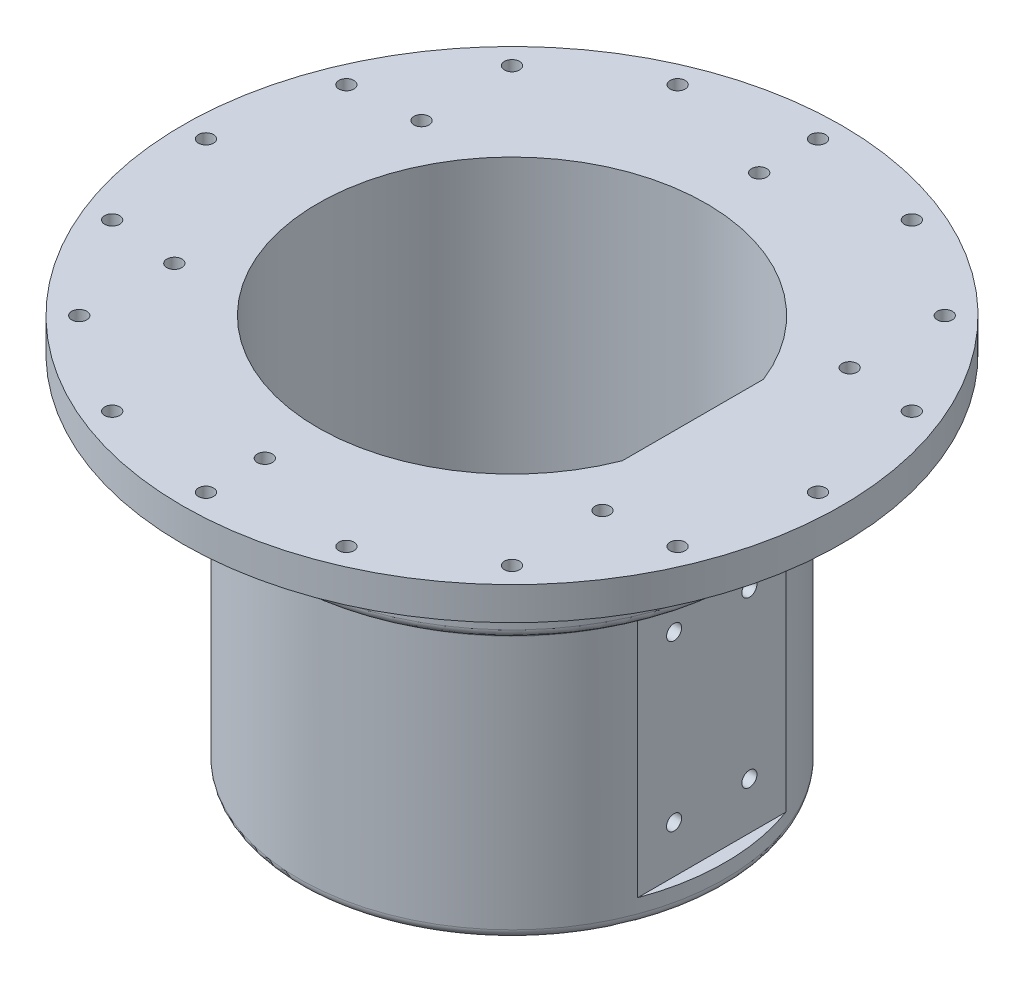
SolidWorks part; units mm, degrees
ref_plane "Front Plane" through (0, 0, 0) normal (0, 0, 1) x (1, 0, 0)
ref_plane "Top Plane" through (0, 0, 0) normal (0, 1, 0) x (1, 0, 0)
ref_plane "Right Plane" through (0, 0, 0) normal (1, 0, 0) x (0, 0, -1)
sketch "Sketch1" plane through (0, 0, 0) normal (0, 1, 0) x (1, 0, 0)
  circle A0 centre (0, 0) radius 49.25
  circle A1 centre (0, 0) radius 55 construction
  circle A2 centre (0, 0) radius 60
  circle A3 centre (0, 0) radius 52.5 construction
  circle A4 centre (0, 52.5) radius 1.6
  circle A5 centre (45.4663, 26.25) radius 1.6
  circle A6 centre (45.4663, -26.25) radius 1.6
  circle A7 centre (0, -52.5) radius 1.6
  circle A8 centre (-45.4663, -26.25) radius 1.6
  circle A9 centre (-45.4663, 26.25) radius 1.6
  point P9 (0, 0)
  point P10 (0, 0)
  point P20 (0, 0)
  dimension "D1" = 110
  dimension "D2" = 98.5
  dimension "D3" = 120
  dimension "D4" = 105
  dimension "D5" = 3.2
  dimension "D6" = 6
extrude "Boss-Extrude1" add sketch "Sketch1" along normal blind 7
sketch "Sketch2" plane through (0, 7, 0) normal (0, 1, 0) x (1, 0, 0)
  line L0 (0, 0) -> (29.4576, 0) construction
  line L1 (29.4576, 12.5) -> (60, 12.5) construction
  line L2 (29.4576, 12.5) -> (29.4576, -12.5) construction
  line L3 (29.4576, -12.5) -> (60, -12.5) construction
  line L4 (60, 12.5) -> (60, -12.5) construction
  circle A0 centre (0, 0) radius 49.25
  circle A2 centre (0, 0) radius 49.25 construction
  circle A3 centre (0, 0) radius 32 construction
  circle A5 centre (0, 0) radius 60 construction
  circle A6 centre (0, 0) radius 45.25
  point P8 (33.7602, 12.5)
  point P19 (33.7602, -12.5)
  circle M6 centre (0, 0) radius 49.25
  dimension "D1" = 4
  dimension "D2" = 64
  dimension "D3" = 25
extrude "Boss-Extrude2" add sketch "Sketch2" against normal blind 25 contours A6 M6 region at (-47.857, 7, 0)
sketch "Sketch6" plane through (0, 7, 0) normal (0, 1, 0) x (1, 0, 0)
  line L1 (38.4261, 15) -> (60, 15)
  line L2 (38.4261, 15) -> (38.4261, -15)
  line L3 (38.4261, -15) -> (60, -15)
  line L4 (60, 15) -> (60, -15)
  circle A0 centre (0, 0) radius 45.25
  circle A1 centre (0, 0) radius 41.25
  circle A2 centre (0, 0) radius 45.25 construction
  circle A3 centre (0, 0) radius 60 construction
  point P10 (0, 0)
  point P11 (38.4261, 0)
  point P14 (38.3377, 11.4114)
  circle M14 centre (0, 0) radius 45.25
  dimension "D1" = 4
  dimension "D2" = 30
extrude "Boss-Extrude5" add sketch "Sketch6" against normal blind 78 contours A1 L1 L3 M14 | L2 A1 | A1 L3 L1 M14 region at (-42.5119, 7, 0) region at (39.559, 7, 0) region at (42.3493, 7, 0)
sketch "Sketch7" plane through (0, -71, 0) normal (0, -1, 0) x (1, 0, 0)
  line L0 (38.4261, -15) -> (38.4261, 15) construction
  line L1 (42.4261, 15.735) -> (60, 15.735)
  line L2 (42.4261, 15.735) -> (42.4261, -15.735)
  line L3 (42.4261, -15.735) -> (60, -15.735)
  line L4 (60, 15.735) -> (60, -15.735)
  circle A0 centre (0, 0) radius 45.25 construction
  circle A1 centre (0, 0) radius 45.25 construction
  circle A2 centre (0, 0) radius 60 construction
  point P6 (41.1316, -15.6267)
  point P9 (42.4261, 0)
  dimension "D1" = 4
extrude "Cut-Extrude3" cut sketch "Sketch7" against normal up to surface (53 mm away) up to face at (0, -18, 45.25)
sketch "Sketch8" plane through (0, -71, 0) normal (0, -1, 0) x (1, 0, 0)
  circle A0 centre (0, 0) radius 45.25
  arc A1 (42.4261, 15.735) -> (42.4261, -15.735) centre (0, 0) ccw construction
  circle A2 centre (0, 0) radius 32
  circle A3 centre (0, 0) radius 37.75 construction
  circle A4 centre (26.6933, 26.6933) radius 1.6
  circle A5 centre (37.75, 0) radius 1.6
  circle A6 centre (26.6933, -26.6933) radius 1.6
  circle A7 centre (0, -37.75) radius 1.6
  circle A8 centre (-26.6933, -26.6933) radius 1.6
  circle A9 centre (-37.75, 0) radius 1.6
  circle A10 centre (-26.6933, 26.6933) radius 1.6
  circle A11 centre (0, 37.75) radius 1.6
  point P10 (0, 0)
  point P11 (36.5, 0)
  point P19 (0, 0)
  dimension "D1" = 7.5
  dimension "D2" = 64
  dimension "D3" = 3.2
  dimension "D4" = 8
extrude "Boss-Extrude6" add sketch "Sketch8" along normal blind 5
sketch "Sketch9" plane through (42.4261, 0, 0) normal (1, 0, 0) x (0, 0, -1)
  line L0 (15.735, -71) -> (-15.735, -71) construction
  line L1 (-8, -26) -> (8, -26) construction
  line L2 (-8, -26) -> (-8, -61) construction
  line L3 (-8, -61) -> (8, -61) construction
  line L4 (8, -26) -> (8, -61) construction
  circle A0 centre (-8, -26) radius 1.6
  circle A1 centre (8, -26) radius 1.6
  circle A2 centre (8, -61) radius 1.6
  circle A3 centre (-8, -61) radius 1.6
  point P4 (0, -26)
  dimension "D4" = 3.2
  dimension "D1" = 16
  dimension "D2" = 35
  dimension "D3" = 10
extrude "Cut-Extrude4" cut sketch "Sketch9" against normal up to surface (4 mm away) up to face at (38.4261, -45, 0)
fillet "Fillet1" radius 2 4 edges at (0, -76, -45.25) (42.4261, -18, 0) (-45.25, -18, 0) (0, -18, 49.25)
sketch "Sketch10" plane through (0, 0, 0) normal (1, 0, 0) x (0, 0, -1)
  line L0 (-49.25, -8) -> (-47.25, -8) construction
  line L1 (-49.25, -6.25) -> (-47.25, -6.25)
  line L2 (-49.25, -6.25) -> (-49.25, -9.75)
  line L3 (-49.25, -9.75) -> (-47.25, -9.75)
  line L4 (-47.25, -6.25) -> (-47.25, -9.75)
  line L5 (-49.25, 0) -> (-49.25, -16) construction
  line L6 (0, 0) -> (0, -16) construction
  line L7 (-49.25, 0) -> (49.25, 0) construction
  line L8 (-49.25, -16) -> (49.25, -16) construction
  dimension "D1" = 2
  dimension "D2" = 3.5
revolve "Cut-Revolve1" cut sketch "Sketch10" angle 360 about L6
sketch "Sketch11" plane through (0, 7, 0) normal (0, 1, 0) x (1, 0, 0)
  circle A0 centre (0, 0) radius 60
  circle A1 centre (0, 0) radius 70
  circle A2 centre (0, 0) radius 60 construction
  circle A3 centre (0, 0) radius 65 construction
  circle A4 centre (0, 65) radius 1.6
  circle A5 centre (24.8744, 60.0522) radius 1.6
  circle A6 centre (45.9619, 45.9619) radius 1.6
  circle A7 centre (60.0522, 24.8744) radius 1.6
  circle A8 centre (65, 0) radius 1.6
  circle A9 centre (60.0522, -24.8744) radius 1.6
  circle A10 centre (45.9619, -45.9619) radius 1.6
  circle A11 centre (24.8744, -60.0522) radius 1.6
  circle A12 centre (0, -65) radius 1.6
  circle A13 centre (-24.8744, -60.0522) radius 1.6
  circle A14 centre (-45.9619, -45.9619) radius 1.6
  circle A15 centre (-60.0522, -24.8744) radius 1.6
  circle A16 centre (-65, 0) radius 1.6
  circle A17 centre (-60.0522, 24.8744) radius 1.6
  circle A18 centre (-45.9619, 45.9619) radius 1.6
  circle A19 centre (-24.8744, 60.0522) radius 1.6
  point P9 (0, 0)
  point P10 (45.9583, 45.9656)
  point P11 (0, 0)
  point P42 (0, 0)
  dimension "D1" = 10
  dimension "D2" = 5
  dimension "D3" = 3.2
  dimension "D4" = 16
extrude "Boss-Extrude7" add sketch "Sketch11" against normal up to surface (7 mm away) up to face at (0, 0, 60)
